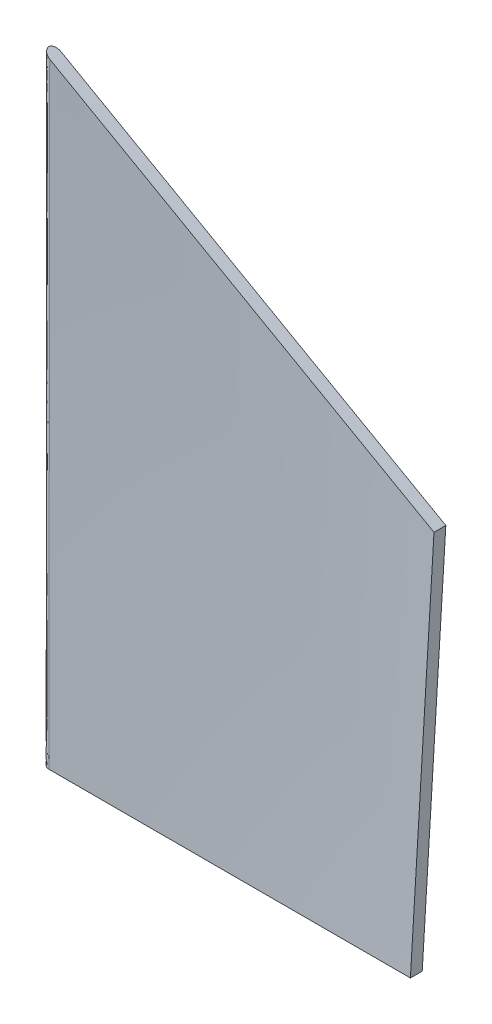
SolidWorks part; units mm, degrees
material "Verre"
ref_plane "Plan de face" through (0, 0, 0) normal (0, 0, 1) x (1, 0, 0)
ref_plane "Plan de dessus" through (0, 0, 0) normal (0, 1, 0) x (1, 0, 0)
ref_plane "Plan de droite" through (0, 0, 0) normal (1, 0, 0) x (0, 0, -1)
sketch "Esquisse1" plane through (0, 0, 0) normal (1, 0, 0) x (0, 0, -1)
  line L1 (311.9526, 1025.8054) -> (356.9526, 1025.8054)
  line L2 (311.9526, 1025.8054) -> (311.9526, -1330.7746)
  line L3 (311.9526, -1330.7746) -> (356.9526, -1330.7746)
  line L4 (356.9526, 1025.8054) -> (356.9526, -1330.7746)
  dimension "D1" = 2356.58
  dimension "D2" = 45
ref_plane "Plan1" through (1400, 0, 0) normal (1, 0, 0) x (0, 0, -1)
sketch "Esquisse2" plane through (1400, 0, 0) normal (1, 0, 0) x (0, 0, -1)
  line L0 (311.9526, -1330.7746) -> (356.9526, -1330.7746)
  line L1 (356.9526, -1330.7746) -> (446.7446, 92.4657)
  line L2 (446.7446, 92.4657) -> (401.7446, 92.4657)
  line L3 (401.7446, 92.4657) -> (311.9526, -1330.7746)
  dimension "D1" = 1426.07
  dimension "D2" = 86.39
loft "Lissage1" add profiles "Esquisse1", "Esquisse2" connector at (0, 1025.8054, -356.9526) connector at (1400, 92.4657, -446.7446)
sketch "Esquisse3" plane through (0, -1330.7746, 0) normal (0, -1, 0) x (1, 0, 0)
  line L1 (0, -311.9526) -> (1400, -311.9526) construction
  line L2 (0, -311.9526) -> (0, -356.9526) construction
  circle A0 centre (10, -334.4526) radius 5
  dimension "D1" = 10
  dimension "D2" = 10
  dimension "D3" = 22.5
extrude "Enlèv. mat.-Extru.1" cut sketch "Esquisse3" against normal blind 20
fillet "Congé1" radius 25 2 edges
